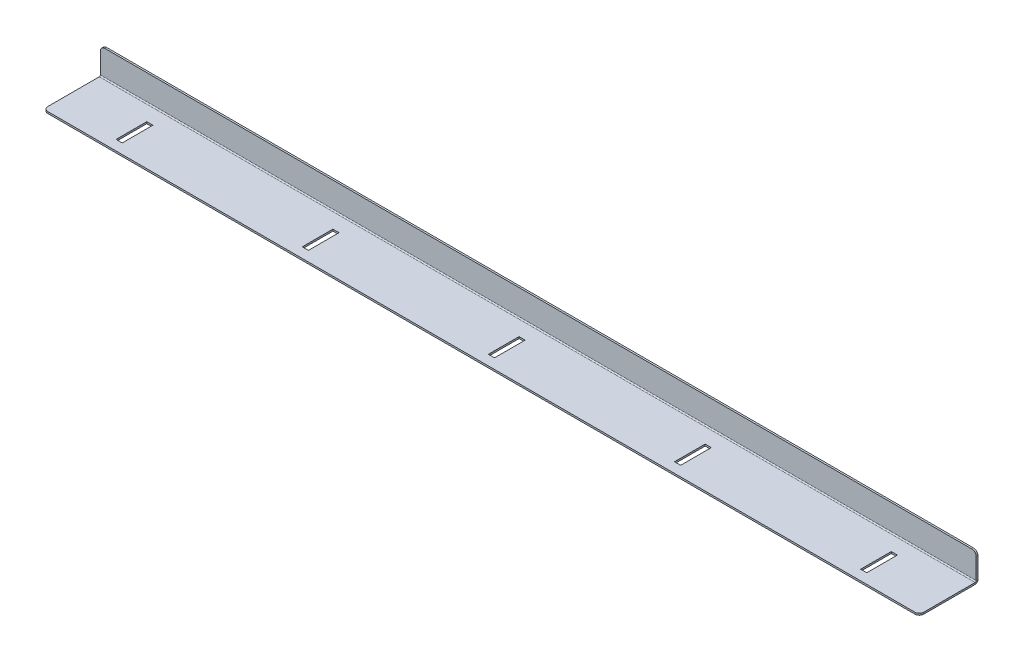
SolidWorks part; units mm, degrees
note: The reader was unsure of these and kept them because the rebuilt part matched: bend radius of "BaseBend4".
material "AISI 304"
ref_plane "Front Plane" through (0, 0, 0) normal (0, 0, 1) x (1, 0, 0)
ref_plane "Top Plane" through (0, 0, 0) normal (0, 1, 0) x (1, 0, 0)
ref_plane "Right Plane" through (0, 0, 0) normal (1, 0, 0) x (0, 0, -1)
sketch "Sketch1" plane through (0, 0, 0) normal (1, 0, 0) x (0, 0, -1)
  line L0 (0, 0) -> (0, 30)
  line L4 (0, 0) -> (-65, 0)
  dimension "D1" = 30
  dimension "D5" = 65
base flange "Base-Flange1" sketch "Sketch1" end condition mid plane depth 1000 reverse direction no thickness 2 reverse thickness direction no bend radius 1.3
bend "BaseBend4" bend radius 1.3 bend angle 90 parameters "D5"=7
fillet "Fillet1" radius 5 4 edges at (500, 30, -1) (500, -1, 65) (-500, -1, 65) (-500, 30, -1)
sketch "Sketch2" plane through (0, 0, 0) normal (0, 1, 0) x (1, 0, 0)
  line L0 (495, 2) -> (-495, 2) construction
  line L2 (-421.5, -53.5) -> (-428.5, -53.5)
  line L3 (-500, -60) -> (-500, -1.3) construction
  line L6 (-421.5, -53.5) -> (-421.5, -18.5)
  line L10 (-209, -53.5) -> (-209, -18.5)
  line L13 (-209, -53.5) -> (-216, -53.5)
  line L16 (-216, -53.5) -> (-216, -18.5)
  line L19 (-209, -18.5) -> (-216, -18.5)
  line L21 (-421.5, -18.5) -> (-428.5, -18.5)
  line L22 (-428.5, -53.5) -> (-428.5, -18.5)
  line L23 (-421.5, -53.5) -> (-428.5, -18.5) construction
  line L24 (-421.5, -18.5) -> (-428.5, -53.5) construction
  line L25 (3.5, -53.5) -> (3.5, -18.5)
  line L26 (3.5, -53.5) -> (-3.5, -53.5)
  line L27 (-3.5, -53.5) -> (-3.5, -18.5)
  line L28 (3.5, -18.5) -> (-3.5, -18.5)
  line L29 (216, -53.5) -> (216, -18.5)
  line L30 (216, -53.5) -> (209, -53.5)
  line L31 (209, -53.5) -> (209, -18.5)
  line L32 (216, -18.5) -> (209, -18.5)
  line L33 (428.5, -53.5) -> (428.5, -18.5)
  line L34 (428.5, -53.5) -> (421.5, -53.5)
  line L35 (421.5, -53.5) -> (421.5, -18.5)
  line L36 (428.5, -18.5) -> (421.5, -18.5)
  line L37 (500, -60) -> (500, -1.3) construction
  point P5 (425, -53.5)
  point P41 (-425, -36)
  dimension "D3" = 5
  dimension "D4" = 75
  dimension "D1" = 20.5
  dimension "D2" = 75
  dimension "D7" = 7
  dimension "D8" = 35
extrude "Cut-Extrude1" cut sketch "Sketch2" against normal blind 10
sketch "Bend-Lines1" [suppressed] plane through (0, 0, 0) normal (0, 1, 0) x (1, 0, 0)
sketch "Bounding-Box1" [suppressed] plane through (0, 0, 0) normal (0, 1, 0) x (1, 0, 0)
sheet metal parameters "Sheet-Metal1" thickness 2 parameters "D1"=2
flat pattern "Flat-Pattern1" [suppressed]
sketch "Bend-Lines2" plane through (0, 0, 0) normal (0, 0, 1) x (1, 0, 0)
  line L6 (500, -0.3423) -> (-500, -0.3423) construction
  line L7 (500, -0.3423) -> (-500, -0.3423) construction
sketch3d "Bounding-Box2" [suppressed]
  line L0 (-1000, 25.0001, 0) -> (0, 25, 0) construction
  line L1 (-1000, -43.6845, 0) -> (0, -43.6845, 0) construction
  line L2 (-1000, 25.0001, 0) -> (-1000, -43.6845, 0) construction
  line L3 (0, 25, 0) -> (0, -43.6845, 0) construction
bend of the flat pattern "Flatten-<BaseBend4>1"
sheet metal parameters "Sheet-Metal2" thickness 2 parameters "D1"=2
flat pattern "Flat-Pattern1"
sketch "Bend-Lines2" plane through (0, 0, 0) normal (0, 0, 1) x (1, 0, 0)
  line L6 (500, -0.3423) -> (-500, -0.3423) construction
  line L7 (500, -0.3423) -> (-500, -0.3423) construction
sketch3d "Bounding-Box2" [suppressed]
  line L0 (-1000, 30.0001, 0) -> (0, 30, 0) construction
  line L1 (-1000, -65.6845, 0) -> (0, -65.6845, 0) construction
  line L2 (-1000, 30.0001, 0) -> (-1000, -65.6845, 0) construction
  line L3 (0, 30, 0) -> (0, -65.6845, 0) construction
bend of the flat pattern "Flatten-<BaseBend4>1"
